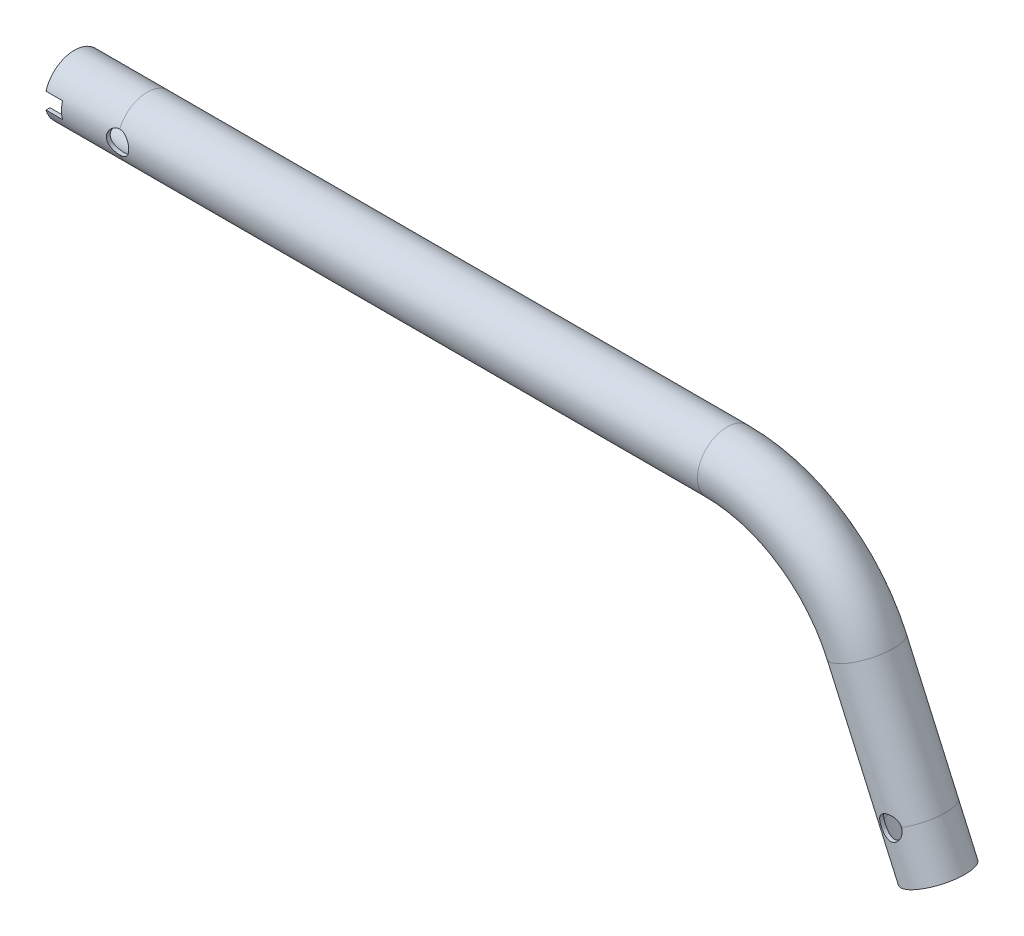
SolidWorks part; units mm, degrees
ref_plane "Front Plane" through (0, 0, 0) normal (0, 0, 1) x (1, 0, 0)
ref_plane "Top Plane" through (0, 0, 0) normal (0, 1, 0) x (1, 0, 0)
ref_plane "Right Plane" through (0, 0, 0) normal (1, 0, 0) x (0, 0, -1)
sketch "Sketch1" plane through (0, 0, 0) normal (0, 0, 1) x (1, 0, 0)
  line L0 (0, 0) -> (181.8886, 0)
  line L1 (225.7388, -28.4766) -> (242, -65)
  line L2 (0, 0) -> (-22.7983, 0)
  line L3 (242, -65) -> (248.101, -78.7032)
  arc A0 (225.7388, -28.4766) -> (181.8886, 0) centre (181.8886, -48) ccw
  point P10 (242, -65)
  dimension "D2" = 48
  dimension "D5" = 15
  dimension "D1" = 66
  dimension "D3" = 242
  dimension "D4" = 65
  dimension "D6" = 181.8886
  dimension "D7" = 22.7983
  dimension "D8" = 54.9798
ref_plane "Plane1" through (-22.7983, 0, 0) normal (-1, 0, 0) x (0, 0, 1)
sketch "Sketch2" plane through (-22.7983, 0, 0) normal (-1, 0, 0) x (0, 0, 1)
  circle A0 centre (0, 0) radius 9.25
  circle A1 centre (0, 0) radius 8.05
  dimension "D1" = 1.2
  dimension "D2" = 18.5
sweep "Sweep1" add profiles "Sketch2" path "Sketch1"
sketch "Sketch3" plane through (0, 0, 0) normal (0, 0, 1) x (1, 0, 0)
  line L0 (233.5497, -68.7623) -> (250.4503, -61.2377) construction
  circle A4 centre (242, -65) radius 3.5
extrude "Cut-Extrude1" cut sketch "Sketch3" against normal up to next and the other way up to next
sketch "Sketch4" plane through (0, 0, 0) normal (0, 0, 1) x (1, 0, 0)
  line L0 (0, -9.25) -> (0, 9.25) construction
  circle A0 centre (0, 0) radius 3.5
  dimension "D1" = 7
extrude "Cut-Extrude2" cut sketch "Sketch4" along normal up to next
sketch "Sketch5" plane through (0, 0, 0) normal (0, 0, 1) x (1, 0, 0)
  line L0 (-22.7983, 0) -> (-22.7983, 2.555)
  line L1 (-22.7983, 9.25) -> (-22.7983, -9.25) construction
  line L2 (-22.7983, 2.555) -> (-17.5983, 2.555)
  line L3 (-17.5983, 2.555) -> (-17.5983, -2.555)
  line L4 (-17.5983, -2.555) -> (-22.7983, -2.555)
  line L5 (-22.7983, -2.555) -> (-22.7983, 0)
  dimension "D1" = 5.2
  dimension "D2" = 5.11
extrude "Cut-Extrude3" cut sketch "Sketch5" against normal through all and the other way through all
